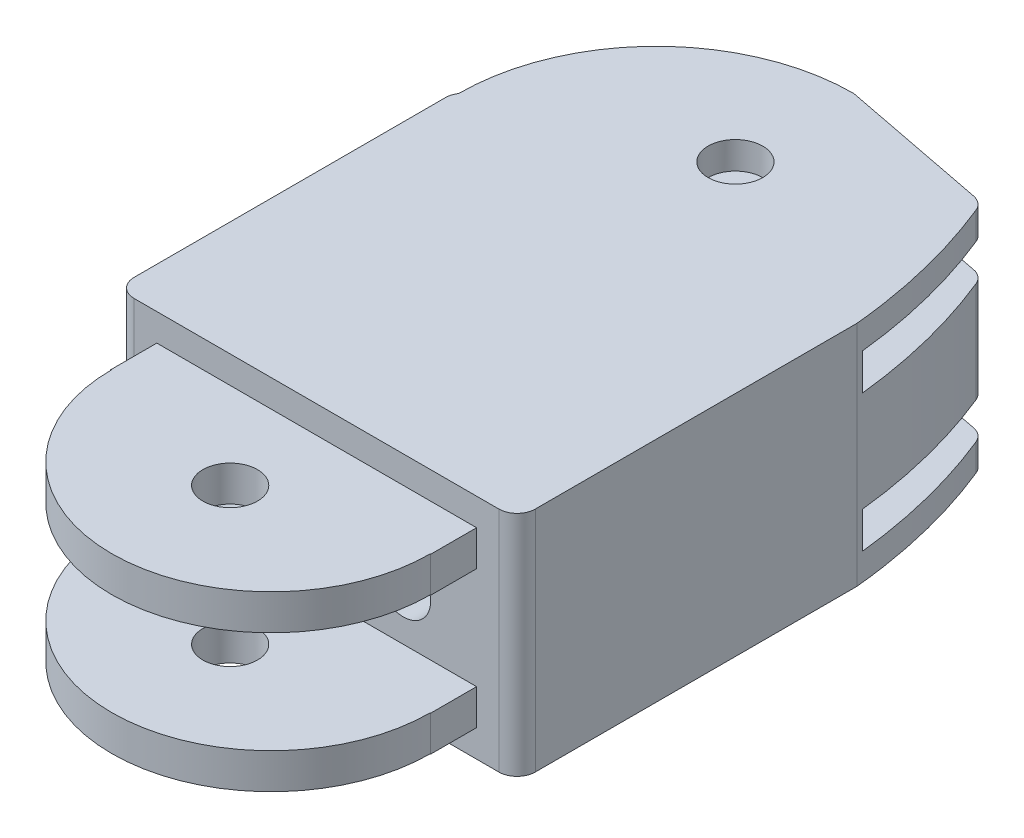
SolidWorks part; units mm, degrees
ref_plane "Front Plane" through (0, 0, 0) normal (0, 0, 1) x (1, 0, 0)
ref_plane "Top Plane" through (0, 0, 0) normal (0, 1, 0) x (1, 0, 0)
ref_plane "Right Plane" through (0, 0, 0) normal (1, 0, 0) x (0, 0, -1)
sketch "Sketch2" plane through (0, 0, 0) normal (0, 0, 1) x (1, 0, 0)
  line L0 (-24.2561, -24.0702) -> (-22.0061, -24.0702) construction
  line L1 (-24.2561, -17.8202) -> (-2.2017, -17.8202) construction
  line L2 (-24.2561, -17.8202) -> (-24.2561, -30.3202) construction
  line L3 (-24.2561, -30.3202) -> (-2.2017, -30.3202) construction
  line L4 (-2.2017, -17.8202) -> (-2.2017, -30.3202) construction
  line L5 (-2.2017, -24.0702) -> (-4.4517, -24.0702) construction
  line L6 (-22.0061, -24.0702) -> (-22.0061, -30.3202) construction
  line L7 (-4.4517, -24.0702) -> (-4.4517, -30.3202) construction
  line L8 (-24.2561, -17.8202) -> (-24.2561, -19.3148) construction
  line L9 (-24.2561, -19.3148) -> (-22.0061, -19.3148) construction
  line L10 (-2.2017, -17.8202) -> (-2.2017, -19.3148) construction
  line L11 (-2.2017, -19.3148) -> (-4.4517, -19.3148) construction
  line L12 (-2.2017, -30.3202) -> (-2.2017, -28.8202) construction
  line L13 (-2.2017, -28.8202) -> (-4.4517, -28.8202) construction
  line L14 (-24.2561, -30.3202) -> (-24.2561, -28.8202) construction
  line L15 (-24.2561, -28.8202) -> (-22.0061, -28.8202) construction
  line L17 (-22.0061, -28.8202) -> (-4.4517, -28.8202)
  line L18 (-22.0061, -28.8202) -> (-22.0061, -26.8702)
  line L19 (-22.0061, -26.8702) -> (-4.4517, -26.8702)
  line L20 (-4.4517, -28.8202) -> (-4.4517, -26.8702)
  line L21 (-22.0061, -28.8202) -> (-4.4517, -26.8702) construction
  line L22 (-22.0061, -26.8702) -> (-4.4517, -28.8202) construction
  line L23 (-22.0061, -19.3148) -> (-4.4517, -19.3148)
  line L24 (-22.0061, -19.3148) -> (-22.0061, -21.2648)
  line L25 (-22.0061, -21.2648) -> (-4.4517, -21.2648)
  line L26 (-4.4517, -19.3148) -> (-4.4517, -21.2648)
  line L27 (-22.0061, -19.3148) -> (-4.4517, -21.2648) construction
  line L28 (-22.0061, -21.2648) -> (-4.4517, -19.3148) construction
  point P19 (-13.2289, -27.8452)
  point P22 (-13.2289, -20.2898)
extrude "Boss-Extrude1" add sketch "Sketch2" along normal blind 8.75
sketch "Sketch3" plane through (0, -19.3148, 0) normal (0, 1, 0) x (1, 0, 0)
  line L0 (-4.4517, 0) -> (-22.0061, 0) construction
  line L1 (-4.4517, -8.75) -> (-22.0061, -8.75) construction
  arc A0 (-13.2289, -8.75) -> (-4.4789, 0) centre (-13.2289, 0) ccw
  arc A1 (-13.2289, -8.75) -> (-21.9789, 0) centre (-13.2289, 0) cw
  spline S0 degree 2 poles (-22.0061, -8.75) (-13.2289, -12.4735) (-4.4517, -8.75) knots 0 0 0 1 1 1
  spline S1 degree 2 poles (-21.9789, 0) (-25.927, -4.2429) (-22.0061, -8.75) knots 0 0 0 1 1 1
  spline S2 degree 2 poles (-4.4789, 0) (1.1383, -4.1517) (-4.4517, -8.75) knots 0 0 0 1 1 1
extrude "Cut-Extrude1" cut sketch "Sketch3" against normal through all contours S0 S2 A0 A1 S1
sketch "Sketch4" plane through (0, 0, 0) normal (0, 0, -1) x (-1, 0, 0)
  line L0 (22.0061, -19.3148) -> (24.2561, -19.3148) construction
  line L1 (22.0061, -19.3148) -> (4.4789, -19.3148) construction
  line L2 (22.0061, -19.3148) -> (22.0061, -28.8202) construction
  line L3 (22.0061, -28.8202) -> (4.4789, -28.8202) construction
  line L4 (4.4789, -19.3148) -> (4.4789, -28.8202) construction
  line L5 (22.0061, -19.3148) -> (4.4789, -28.8202) construction
  line L6 (22.0061, -28.8202) -> (4.4789, -19.3148) construction
  line L7 (24.2561, -19.3148) -> (24.2561, -17.8148) construction
  line L8 (4.4789, -28.8202) -> (2.2289, -28.8202) construction
  line L9 (2.2289, -28.8202) -> (2.2289, -30.3202) construction
  line L11 (24.2561, -17.8148) -> (2.2289, -17.8148)
  line L12 (24.2561, -17.8148) -> (24.2561, -30.3202)
  line L13 (24.2561, -30.3202) -> (2.2289, -30.3202)
  line L14 (2.2289, -17.8148) -> (2.2289, -30.3202)
  line L15 (24.2561, -17.8148) -> (2.2289, -30.3202) construction
  line L16 (24.2561, -30.3202) -> (2.2289, -17.8148) construction
  point P4 (13.2425, -24.0675)
  point P14 (13.2425, -24.0675)
extrude "Boss-Extrude2" add sketch "Sketch4" along normal blind 32 contours L12 L13 L14 L11
sketch "Sketch5" plane through (0, -19.3148, 0) normal (0, 1, 0) x (1, 0, 0)
  line L0 (-13.2289, -8.75) -> (-13.2289, -2.25) construction
  arc A0 (-21.9789, 0) -> (-4.4789, 0) centre (-13.2289, 0) ccw construction
  circle A1 centre (-13.2289, -2.25) radius 1.5
extrude "Cut-Extrude2" cut sketch "Sketch5" against normal blind 12 contours A1
sketch "Sketch6" plane through (0, 0, 0) normal (0, 0, 1) x (1, 0, 0)
  line L0 (-24.2561, -30.3202) -> (-2.2289, -30.3202)
  line L1 (-2.2289, -30.3202) -> (-2.2289, -17.8148)
  line L2 (-2.2289, -17.8148) -> (-24.2561, -17.8148)
  line L3 (-24.2561, -17.8148) -> (-24.2561, -30.3202)
  line L4 (-22.0061, -28.8202) -> (-4.4517, -28.8202)
  line L5 (-4.4517, -28.8202) -> (-4.4517, -26.8702)
  line L6 (-4.4517, -28.8202) -> (-4.4517, -26.8702) construction
  line L7 (-4.4517, -26.8702) -> (-22.0061, -26.8702)
  line L8 (-22.0061, -28.8202) -> (-22.0061, -26.8702)
  line L9 (-22.0061, -21.2648) -> (-22.0061, -19.3148)
  line L10 (-22.0061, -19.3148) -> (-4.4517, -19.3148)
  line L11 (-4.4517, -19.3148) -> (-4.4517, -21.2648)
  line L12 (-4.4517, -21.2648) -> (-22.0061, -21.2648)
extrude "Cut-Extrude3" cut sketch "Sketch6" against normal blind 2.5
sketch "Sketch7" plane through (0, -17.8148, 0) normal (0, 1, 0) x (1, 0, 0)
  line L0 (-13.2425, 32) -> (-13.2425, 25.5) construction
  line L1 (-24.2561, 32) -> (-2.2289, 32) construction
  line L2 (-13.2425, 25.5) -> (-13.2425, 21.1557) construction
  line L3 (-24.0869, 21.1557) -> (-24.2561, 21.1557)
  line L4 (-24.2561, 32) -> (-24.2561, 2.5) construction
  line L6 (-2.2289, 32) -> (-2.2289, 2.5) construction
  line L7 (-13.2425, 32) -> (-4.5527, 30.3114)
  circle A0 centre (-13.2425, 25.5) radius 1.5
  arc A1 (-13.2425, 32) -> (-24.0869, 21.1557) centre (-13.2425, 21.1557) ccw
  spline S0 degree 3 poles (-2.2289, 21.1557) (11.4715, 27.1897) (-11.7652, 53.4313) (-37.0079, 21.5236) (-24.2561, 21.1557) knots 0 0 0 0 0.520113 1 1 1 1
  spline S1 degree 2 poles (-4.5527, 30.3114) (-2.6852, 25.9285) (-2.2289, 21.1557) knots 0 0 0 1 1 1
  point P17 (-4.609, 29.9532)
  point P19 (-3.3799, 27.0681)
  point P20 (-4.5527, 30.3114)
  point P21 (0, 0)
extrude "Cut-Extrude4" cut sketch "Sketch7" against normal blind 13
sketch "Sketch8" plane through (0, 0, -2.5) normal (0, 0, 1) x (1, 0, 0)
  line L0 (-24.2561, -24.0675) -> (-18.0111, -24.0675) construction
  line L1 (-24.2561, -17.8148) -> (-24.2561, -30.3202) construction
  line L2 (-2.2289, -24.0675) -> (-8.474, -24.0675) construction
  line L3 (-2.2289, -30.3202) -> (-2.2289, -17.8148) construction
  line L4 (-4.4517, -21.2648) -> (-4.4517, -24.0675) construction
  line L5 (-4.4517, -24.0675) -> (-8.474, -24.0675) construction
  circle A0 centre (-18.0111, -24.0675) radius 1.5
  circle A1 centre (-8.474, -24.0675) radius 1.5
extrude "Cut-Extrude5" cut sketch "Sketch8" against normal blind 28
fillet "Fillet3" radius 1 4 edges at (-24.2561, -24.0675, -2.5) (-24.2561, -24.0675, -21.1557) (-2.2289, -24.0675, -2.5) (-4.5527, -24.0675, -30.3114)
ref_plane "Plane4" through (0, 0, -32.5) normal (0, 0, 1) x (1, 0, 0)
sketch "Sketch9" plane through (0, 0, -32.5) normal (0, 0, 1) x (1, 0, 0)
  line L0 (-24.2561, -17.8148) -> (-24.2561, -19.3148) construction
  line L1 (-24.2561, -17.8148) -> (-2.2289, -17.8148) construction
  line L2 (-24.2561, -17.8148) -> (-24.2561, -30.3202) construction
  line L3 (-24.2561, -30.3202) -> (-2.2289, -30.3202) construction
  line L4 (-2.2289, -17.8148) -> (-2.2289, -30.3202) construction
  line L5 (-24.2561, -17.8148) -> (-2.2289, -30.3202) construction
  line L6 (-24.2561, -30.3202) -> (-2.2289, -17.8148) construction
  line L7 (-24.2561, -30.3202) -> (-24.2561, -28.8361) construction
  line L8 (-24.2561, -19.3148) -> (-2.2289, -19.3148)
  line L9 (-24.2561, -19.3148) -> (-24.2561, -21.3148)
  line L10 (-24.2561, -21.3148) -> (-2.2289, -21.3148)
  line L11 (-2.2289, -19.3148) -> (-2.2289, -21.3148)
  line L12 (-24.2561, -19.3148) -> (-2.2289, -21.3148) construction
  line L13 (-24.2561, -21.3148) -> (-2.2289, -19.3148) construction
  line L15 (-24.2561, -28.8361) -> (-2.2289, -28.8361)
  line L16 (-24.2561, -28.8361) -> (-24.2561, -26.8361)
  line L17 (-24.2561, -26.8361) -> (-2.2289, -26.8361)
  line L18 (-2.2289, -28.8361) -> (-2.2289, -26.8361)
  line L19 (-24.2561, -28.8361) -> (-2.2289, -26.8361) construction
  line L20 (-24.2561, -26.8361) -> (-2.2289, -28.8361) construction
  point P4 (-13.2425, -24.0675)
  point P8 (-13.2425, -20.3148)
  point P13 (-13.2425, -27.8361)
extrude "Cut-Extrude6" cut sketch "Sketch9" along normal blind 11
